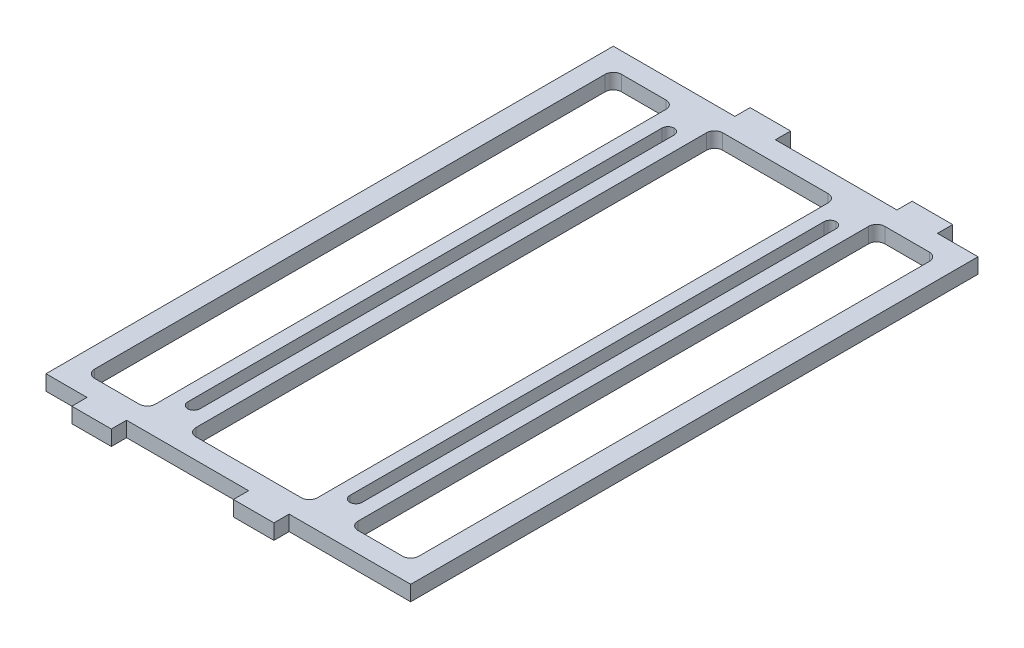
SolidWorks part; units mm, degrees
material "6061-T6 (SS)"
ref_plane "Front Plane" through (0, 0, 0) normal (0, 0, 1) x (1, 0, 0)
ref_plane "Top Plane" through (0, 0, 0) normal (0, 1, 0) x (1, 0, 0)
ref_plane "Right Plane" through (0, 0, 0) normal (1, 0, 0) x (0, 0, -1)
sketch "Sketch1" plane through (0, 0, 0) normal (0, 1, 0) x (1, 0, 0)
  line L0 (50.8, 82.55) -> (-50.8, 82.55)
  line L1 (57.15, 88.9) -> (-57.15, 88.9)
  line L2 (57.15, 88.9) -> (57.15, -88.9)
  line L3 (57.15, -88.9) -> (-57.15, -88.9)
  line L4 (-57.15, 88.9) -> (-57.15, -88.9)
  line L5 (57.15, 88.9) -> (-57.15, -88.9) construction
  line L6 (57.15, -88.9) -> (-57.15, 88.9) construction
  line L7 (-50.8, 82.55) -> (-50.8, -82.55)
  line L8 (50.8, -82.55) -> (-50.8, -82.55)
  line L9 (50.8, 82.55) -> (50.8, -82.55)
  point P0 (0, 0)
  dimension "D1" = 114.3
  dimension "D2" = 177.8
  dimension "D3" = 6.35
extrude "Boss-Extrude1" add sketch "Sketch1" along normal blind 4.7625
sketch "Sketch2" plane through (0, 0, 88.9) normal (0, 0, 1) x (1, 0, 0)
  line L0 (-57.15, 2.3813) -> (57.15, 2.3813) construction
  line L1 (-57.15, 4.7625) -> (-57.15, 0) construction
  line L2 (57.15, 4.7625) -> (57.15, 0) construction
  line L3 (-57.15, 0) -> (57.15, 0) construction
  line L4 (-31.9066, 4.7625) -> (-44.2934, 4.7625)
  line L5 (-31.9066, 4.7625) -> (-31.9066, 0)
  line L6 (-31.9066, 0) -> (-44.2934, 0)
  line L7 (-44.2934, 4.7625) -> (-44.2934, 0)
  line L8 (-31.9066, 4.7625) -> (-44.2934, 0) construction
  line L9 (-31.9066, 0) -> (-44.2934, 4.7625) construction
  line L11 (19.05, 4.7625) -> (6.35, 4.7625)
  line L12 (19.05, 4.7625) -> (19.05, 0)
  line L13 (19.05, 0) -> (6.35, 0)
  line L14 (6.35, 4.7625) -> (6.35, 0)
  line L15 (19.05, 4.7625) -> (6.35, 0) construction
  line L16 (19.05, 0) -> (6.35, 4.7625) construction
  point P6 (-38.1, 2.3813)
  point P13 (12.7, 2.3813)
  dimension "D1" = 19.05
  dimension "D2" = 50.8
  dimension "D3" = 12.7
extrude "Boss-Extrude2" add sketch "Sketch2" along normal blind 4.7625
sketch "Sketch3" plane through (0, 0, -88.9) normal (0, 0, -1) x (-1, 0, 0)
  line L0 (-57.15, 2.3813) -> (57.15, 2.3813) construction
  line L1 (-57.15, 4.7625) -> (-57.15, 0) construction
  line L2 (57.15, 4.7625) -> (57.15, 0) construction
  line L3 (-57.15, 0) -> (57.15, 0) construction
  line L4 (-31.75, 4.7625) -> (-44.45, 4.7625)
  line L5 (-31.75, 4.7625) -> (-31.75, 0)
  line L6 (-31.75, 0) -> (-44.45, 0)
  line L7 (-44.45, 4.7625) -> (-44.45, 0)
  line L8 (-31.75, 4.7625) -> (-44.45, 0) construction
  line L9 (-31.75, 0) -> (-44.45, 4.7625) construction
  line L11 (19.05, 4.7625) -> (6.35, 4.7625)
  line L12 (19.05, 4.7625) -> (19.05, 0)
  line L13 (19.05, 0) -> (6.35, 0)
  line L14 (6.35, 4.7625) -> (6.35, 0)
  line L15 (19.05, 4.7625) -> (6.35, 0) construction
  line L16 (19.05, 0) -> (6.35, 4.7625) construction
  point P6 (-38.1, 2.3812)
  point P13 (12.7, 2.3812)
  dimension "D1" = 12.7
  dimension "D2" = 12.7
  dimension "D3" = 19.05
  dimension "D4" = 50.8
extrude "Boss-Extrude3" add sketch "Sketch3" along normal blind 4.7625
fillet "Fillet1" radius 2.54 4 edges at (50.8, 2.3813, 82.55) (50.8, 2.3813, -82.55) (-50.8, 2.3813, -82.55) (-50.8, 2.3813, 82.55)
sketch "Sketch4" plane through (0, 4.7625, 0) normal (0, 1, 0) x (1, 0, 0)
  line L0 (-57.15, 9.525) -> (57.15, 9.525) construction
  line L1 (-57.15, 88.9) -> (-57.15, -88.9) construction
  line L2 (57.15, -88.9) -> (57.15, 88.9) construction
  line L3 (-57.15, -9.525) -> (57.15, -9.525) construction
  line L5 (50.8, 12.7) -> (-50.8, 12.7)
  line L6 (50.8, 12.7) -> (50.8, 6.35)
  line L7 (50.8, 6.35) -> (-50.8, 6.35)
  line L8 (-50.8, 12.7) -> (-50.8, 6.35)
  line L9 (50.8, 12.7) -> (-50.8, 6.35) construction
  line L10 (50.8, 6.35) -> (-50.8, 12.7) construction
  line L11 (57.15, -6.35) -> (-57.15, -6.35)
  line L12 (57.15, -6.35) -> (57.15, -12.7)
  line L13 (57.15, -12.7) -> (-57.15, -12.7)
  line L14 (-57.15, -6.35) -> (-57.15, -12.7)
  line L15 (57.15, -6.35) -> (-57.15, -12.7) construction
  line L16 (57.15, -12.7) -> (-57.15, -6.35) construction
  point P8 (0, 9.525)
  point P14 (0, -9.525)
  dimension "D1" = 9.525
  dimension "D2" = 9.525
  dimension "D3" = 6.35
  dimension "D4" = 6.35
extrude "Boss-Extrude4" [suppressed] add sketch "Sketch4" against normal blind 4.7625
fillet "Fillet2" [suppressed] radius 2.54
hole_wizard "#6 Clearance Hole1" [suppressed] positions "Sketch6" profile "Sketch5" hole size "#6" standard "Ansi Inch"
sketch "Sketch6" plane through (0, 4.7625, 0) normal (0, 1, 0) x (-1, 0, 0)
  line L1 (-25.4, -9.525) -> (25.4, -9.525)
  line L2 (-25.4, -9.525) -> (-25.4, 9.525)
  line L3 (-25.4, 9.525) -> (25.4, 9.525)
  line L4 (25.4, -9.525) -> (25.4, 9.525)
  line L5 (-25.4, -9.525) -> (25.4, 9.525) construction
  line L6 (-25.4, 9.525) -> (25.4, -9.525) construction
  point P0 (25.4, -9.525)
  point P53 (25.4, 9.525)
  point P55 (-25.4, 9.525)
  point P57 (-25.4, -9.525)
  dimension "D1" = 50.8
  dimension "D2" = 19.05
sketch "Sketch5" plane through (-25.4, 4.7625, -9.525) normal (1, 0, 0) x (0, 0, 1)
  line L0 (0, 0) -> (0, 26.5408)
  line L1 (0, 26.5408) -> (1.8986, 25.4)
  line L2 (1.8986, 25.4) -> (1.8986, 0)
  line L5 (1.8986, 0) -> (0, 0)
  line L10 (0, 26.5408) -> (-1.8986, 25.4) construction
  line L11 (0, -6.35) -> (0, 107.95) construction
  dimension "Hole Dia." = 3.7973
  dimension "Hole Depth" = 25.4
  dimension "Drill Angle" = 118
sketch "Sketch7" plane through (0, 4.7625, 0) normal (0, 1, 0) x (1, 0, 0)
  line L0 (-57.15, 0) -> (57.15, 0) construction
  line L1 (-57.15, 88.9) -> (-57.15, -88.9) construction
  line L2 (57.15, -88.9) -> (57.15, 88.9) construction
  line L3 (-48.26, -82.55) -> (48.26, -82.55) construction
  line L4 (-19.05, 82.55) -> (-31.75, 82.55)
  line L5 (-19.05, 82.55) -> (-19.05, -82.55)
  line L6 (-19.05, -82.55) -> (-31.75, -82.55)
  line L7 (-31.75, 82.55) -> (-31.75, -82.55)
  line L8 (-19.05, 82.55) -> (-31.75, -82.55) construction
  line L9 (-19.05, -82.55) -> (-31.75, 82.55) construction
  line L11 (31.75, 82.55) -> (19.05, 82.55)
  line L12 (31.75, 82.55) -> (31.75, -82.55)
  line L13 (31.75, -82.55) -> (19.05, -82.55)
  line L14 (19.05, 82.55) -> (19.05, -82.55)
  line L15 (31.75, 82.55) -> (19.05, -82.55) construction
  line L16 (31.75, -82.55) -> (19.05, 82.55) construction
  line L17 (-23.495, 76.2) -> (-27.305, 76.2)
  line L18 (-23.495, 76.2) -> (-23.495, -76.2)
  line L19 (-23.495, -76.2) -> (-27.305, -76.2)
  line L20 (-27.305, 76.2) -> (-27.305, -76.2)
  line L21 (-23.495, 76.2) -> (-27.305, -76.2) construction
  line L22 (-23.495, -76.2) -> (-27.305, 76.2) construction
  line L23 (27.305, 76.2) -> (23.495, 76.2)
  line L24 (27.305, 76.2) -> (27.305, -76.2)
  line L25 (27.305, -76.2) -> (23.495, -76.2)
  line L26 (23.495, 76.2) -> (23.495, -76.2)
  line L27 (27.305, 76.2) -> (23.495, -76.2) construction
  line L28 (27.305, -76.2) -> (23.495, 76.2) construction
  point P6 (-25.4, 0)
  point P13 (25.4, 0)
  point P18 (-25.4, 0)
  point P24 (25.4, 0)
  dimension "D1" = 25.4
  dimension "D2" = 12.7
  dimension "D3" = 12.7
  dimension "D4" = 25.4
  dimension "D5" = 3.81
  dimension "D6" = 152.4
  dimension "D7" = 3.81
  dimension "D8" = 152.4
extrude "Boss-Extrude6" add sketch "Sketch7" against normal blind 4.7625
fillet "Fillet3" radius 2.54 8 edges at (31.75, 2.3813, 82.55) (31.75, 2.3813, -82.55) (-19.05, 2.3813, 82.55) (19.05, 2.3813, 82.55) (-31.75, 2.3813, 82.55) (19.05, 2.3813, -82.55) (-19.05, 2.3813, -82.55) (-31.75, 2.3813, -82.55)
fillet "Fillet4" radius 1.905 8 edges at (27.305, 2.3813, -76.2) (23.495, 2.3813, -76.2) (27.305, 2.3813, 76.2) (23.495, 2.3813, 76.2) (-23.495, 2.3813, 76.2) (-27.305, 2.3813, 76.2) (-23.495, 2.3813, -76.2) (-27.305, 2.3813, -76.2)
